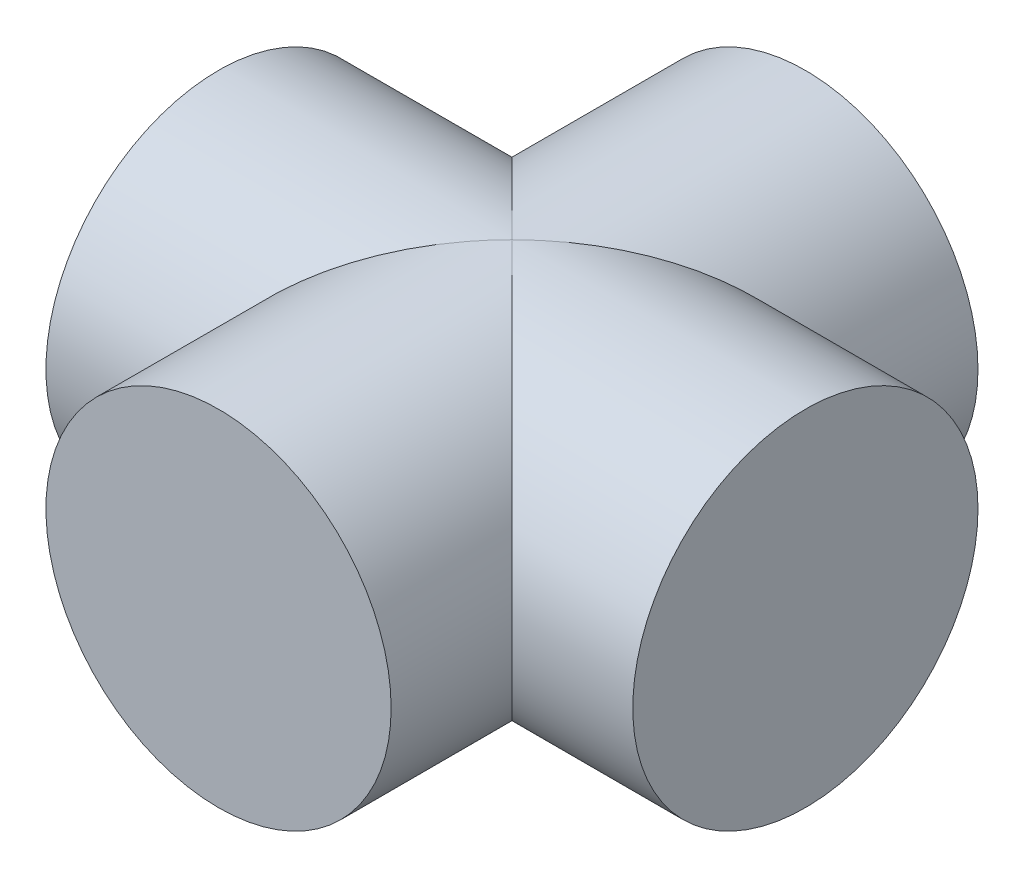
SolidWorks part; units mm, degrees
ref_plane "Front Plane" through (0, 0, 0) normal (0, 0, 1) x (1, 0, 0)
ref_plane "Top Plane" through (0, 0, 0) normal (0, 1, 0) x (1, 0, 0)
ref_plane "Right Plane" through (0, 0, 0) normal (1, 0, 0) x (0, 0, -1)
sketch "Sketch1" plane through (0, 0, 0) normal (0, 0, 1) x (1, 0, 0)
  circle A0 centre (0, 0) radius 7.5
extrude "Boss-Extrude1" add sketch "Sketch1" along normal blind 25.5
sketch "Sketch2" plane through (0, 0, 0) normal (1, 0, 0) x (0, 0, -1)
  line L0 (-12.75, 7.5) -> (-12.75, -7.5) construction
  line L1 (0, 7.5) -> (-25.5, 7.5) construction
  line L2 (-25.5, -7.5) -> (0, -7.5) construction
  line L3 (0, 0) -> (-25.5, 0) construction
  line L4 (-25.5, 7.5) -> (-25.5, -7.5) construction
  circle A0 centre (-12.75, 0) radius 7.5
extrude "Boss-Extrude2" add sketch "Sketch2" along normal blind 12.75 and the other way blind 12.75
